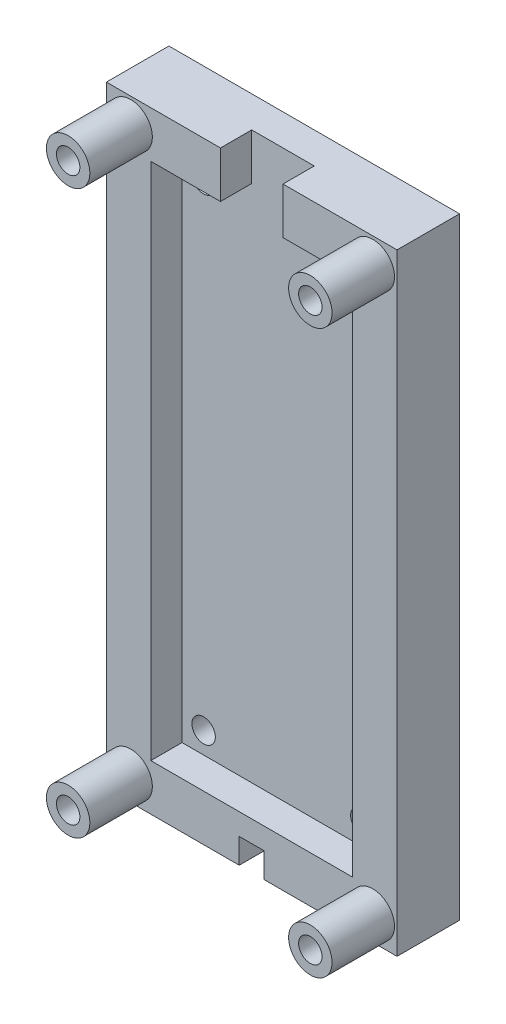
SolidWorks part; units mm, degrees
ref_plane "Front Plane" through (0, 0, 0) normal (0, 0, 1) x (1, 0, 0)
ref_plane "Top Plane" through (0, 0, 0) normal (0, 1, 0) x (1, 0, 0)
ref_plane "Right Plane" through (0, 0, 0) normal (1, 0, 0) x (0, 0, -1)
sketch "Sketch2" plane through (0, 0, 0) normal (0, 0, 1) x (1, 0, 0)
  line L0 (-7.1, -7.425) -> (-7.1, 90.475)
  line L1 (0, 0) -> (32.3, 0)
  line L2 (0, 0) -> (0, 83.05)
  line L3 (0, 83.05) -> (32.3, 83.05)
  line L4 (32.3, 0) -> (32.3, 83.05)
  line L5 (0, 0) -> (32.3, 83.05) construction
  line L6 (0, 83.05) -> (32.3, 0) construction
  line L7 (-7.1, 90.475) -> (39.4, 90.475)
  line L8 (39.4, -7.425) -> (39.4, 90.475)
  line L9 (-7.1, -7.425) -> (39.4, -7.425)
  line L10 (16.15, 3.425) -> (16.15, 79.625) construction
  line L11 (3.45, 79.625) -> (28.85, 79.625)
  line L12 (3.45, 79.625) -> (3.45, 3.425)
  line L13 (3.45, 3.425) -> (28.85, 3.425)
  line L14 (28.85, 79.625) -> (28.85, 3.425)
  line L15 (3.45, 79.625) -> (28.85, 3.425) construction
  line L16 (3.45, 3.425) -> (28.85, 79.625) construction
  line L17 (16.15, 0) -> (16.15, -7.425) construction
  line L18 (0, 41.525) -> (-7.1, 41.525) construction
  point P4 (16.15, 41.525)
  point P10 (16.15, 41.525)
  dimension "D1" = 83.05
  dimension "D2" = 32.3
  dimension "D4" = 25.4
  dimension "D5" = 76.2
  dimension "D3" = 46.5
  dimension "D6" = 97.9
extrude "Boss-Extrude1" add sketch "Sketch2" along normal mid plane 10 contours L0 L9 L8 L7 L4 L1 L2 L3 region at (-6.0162, 41.525, 0)
extrude "Boss-Extrude2" add sketch "Sketch2<4>" against normal blind 5 contours L14 L11 L12 L13 | L1 L4 L3 L2 L11 L14 L13 L12 region at (0.8911, 41.525, 0) region at (16.15, 41.525, 0)
sketch "Sketch2<4>" plane through (0, 0, 0) normal (0, 0, 1) x (1, 0, 0) same geometry as "Sketch2"
ref_axis "Axis1" through (16.15, 3.425, 0) along (0, 1, 0)
sketch "Sketch3" plane through (-7.1, 0, 0) normal (-1, 0, 0) x (0, 0, 1)
  line L0 (-5, -7.425) -> (-5, 90.475) construction
  line L1 (-5, 76.725) -> (5, 76.725)
  line L2 (-5, 76.725) -> (-5, 74.225)
  line L3 (-5, 74.225) -> (5, 74.225)
  line L4 (5, 76.725) -> (5, 74.225)
  line L5 (-5, 76.725) -> (5, 74.225) construction
  line L6 (-5, 74.225) -> (5, 76.725) construction
  line L7 (5, -7.425) -> (5, 90.475) construction
  line L8 (-5, 41.525) -> (5, 41.525) construction
  line L9 (-5, 8.825) -> (5, 8.825)
  line L10 (5, 6.325) -> (5, 8.825)
  line L11 (-5, 6.325) -> (5, 6.325)
  line L12 (-5, 6.325) -> (-5, 8.825)
  line L14 (5, 90.475) -> (-5, 90.475) construction
  point P4 (0, 75.475)
  dimension "D1" = 2.5
  dimension "D2" = 15
extrude "Boss-Extrude3" [suppressed] add sketch "Sketch3" along normal blind 2.5
ref_plane "Plane1" through (16.15, 0, 0) normal (-1, 0, 0) x (0, 0, 1)
chamfer "Chamfer1" [suppressed] distance 0.5 angle 45
mirror "Mirror2" [suppressed] about plane through (16.15, 0, 0) normal (-1, 0, 0)
sketch "Sketch4" plane through (0, 0, 0) normal (0, 0, 1) x (1, 0, 0)
  point P0 (3.45, 79.625)
  point P3 (28.85, 79.625)
  point P6 (3.45, 3.425)
  point P9 (28.85, 3.425)
hole_wizard "telemetrum-holes" positions "Sketch4" profile "Sketch5" hole size "M3x0.5" standard "ANSI Metric" end condition through all
sketch "Sketch5" plane through (3.45, 79.625, 0) normal (1, 0, 0) x (0, -1, 0)
  line L0 (0, 0) -> (0, 5)
  line L1 (0, 5) -> (1.875, 5)
  line L2 (1.875, 5) -> (1.875, 0)
  line L5 (1.875, 0) -> (0, 0)
  line L11 (0, -6.35) -> (0, 107.95) construction
  dimension "Thru Hole Dia." = 3.75
  dimension "Thru Hole Depth" = 5
sketch "Sketch7" plane through (0, 0, 0) normal (0, 0, 1) x (1, 0, 0)
  line L0 (16.15, 5.5) -> (16.15, -5.5) construction
  line L1 (-3.225, 86.525) -> (35.525, 86.525)
  line L2 (-3.225, 86.525) -> (-3.225, -3.475)
  line L3 (-3.225, -3.475) -> (35.525, -3.475)
  line L4 (35.525, 86.525) -> (35.525, -3.475)
  line L5 (16.15, -3.475) -> (16.15, 86.525) construction
  line L6 (-3.225, 41.525) -> (35.525, 41.525) construction
  line L7 (9.5243, 83.05) -> (9.5243, 86.525) construction
  line L8 (0, 83.05) -> (32.3, 83.05) construction
  line L9 (9.5243, -3.475) -> (9.5243, 0) construction
  line L10 (0, 0) -> (32.3, 0) construction
  circle A0 centre (-3.225, 86.525) radius 1.875
  circle A1 centre (35.525, 86.525) radius 1.875
  circle A2 centre (35.525, -3.475) radius 1.875
  circle A3 centre (-3.225, -3.475) radius 1.875
  circle A4 centre (-3.225, 86.525) radius 3.475
  circle A5 centre (35.525, 86.525) radius 3.475
  circle A6 centre (-3.225, -3.475) radius 3.475
  circle A7 centre (35.525, -3.475) radius 3.475
  point P480 (16.15, 41.525)
  dimension "D4" = 3.75
  dimension "D1" = 38.75
  dimension "D2" = 90
  dimension "D3" = 9.5243
  dimension "D5" = 1.6
extrude "standoffs" add sketch "Sketch7" along normal blind 15 contours L2 A6 L3 A3 | L3 A6 L2 A3 | A4 | A0 | A5 | A1 | A2 | A7 region at (-1.4713, -1.7213, 0) region at (-3.3233, -0.8, 0)
sketch "Sketch6" plane through (0, 90.475, 0) normal (0, 1, 0) x (1, 0, 0)
  line L4 (-12.2839, -5.4418) -> (-12.3348, -5.4418)
  line L5 (44.5642, -5.5441) -> (44.6151, -5.5441)
  arc A0 (44.6151, -5.5441) -> (-12.3348, -5.4418) centre (16.15, 0) cw
  arc A1 (44.5642, -5.5441) -> (-12.2839, -5.4418) centre (16.15, 0) cw
  arc A2 (44.566, -5.5346) -> (-12.2857, -5.4325) centre (16.15, 0) cw construction
  dimension "D1" = 29
  dimension "D2" = 0.05
extrude "limit-extrude" add sketch "Sketch6" against normal blind 97.55 separate body
extrude "limit-cut" cut sketch "Sketch6<2>" against normal through all both and the other way through all
sketch "Sketch6<2>" plane through (0, 90.475, 0) normal (0, 1, 0) x (1, 0, 0) same geometry as "Sketch6"
sketch "Sketch11" plane through (0, 0, 5) normal (0, 0, 1) x (1, 0, 0)
  line L0 (0, 83.05) -> (32.3, 83.05) construction
  line L1 (11.15, 75.55) -> (21.15, 75.55)
  line L2 (11.15, 75.55) -> (11.15, 90.55)
  line L3 (11.15, 90.55) -> (21.15, 90.55)
  line L4 (21.15, 75.55) -> (21.15, 90.55)
  line L5 (11.15, 75.55) -> (21.15, 90.55) construction
  line L6 (11.15, 90.55) -> (21.15, 75.55) construction
  point P0 (16.15, 83.05)
  dimension "D1" = 10
  dimension "D2" = 15
extrude "antenna-passthrough" cut sketch "Sketch11" against normal up to surface (5 mm away) and the other way through all up to face at (5.325, 79.625, 0)
sketch "Sketch12" plane through (0, 0, 5) normal (0, 0, 1) x (1, 0, 0)
  line L0 (-7.1, -7.425) -> (39.4, -7.425) construction
  line L1 (18.15, -11.425) -> (14.15, -11.425)
  line L2 (18.15, -11.425) -> (18.15, -3.425)
  line L3 (18.15, -3.425) -> (14.15, -3.425)
  line L4 (14.15, -11.425) -> (14.15, -3.425)
  line L5 (18.15, -11.425) -> (14.15, -3.425) construction
  line L6 (18.15, -3.425) -> (14.15, -11.425) construction
  point P0 (16.15, -7.425)
  dimension "D1" = 8
  dimension "D2" = 4
extrude "battery-passthrough" cut sketch "Sketch12" against normal through all
sketch "Sketch13" plane through (0, 0, 5) normal (0, 0, 1) x (1, 0, 0)
  line L0 (-3.55, 41.525) -> (35.85, 41.525)
  line L1 (16.15, 41.525) -> (16.15, 90.475) construction
  line L2 (11.15, 90.475) -> (21.15, 90.475) construction
  line L3 (16.15, 41.525) -> (16.15, -3.425) construction
  line L4 (18.15, -3.425) -> (14.15, -3.425) construction
  line L5 (-3.55, 90.475) -> (-3.55, -7.425) construction
  line L6 (-7.1, 90.475) -> (11.15, 90.475) construction
  line L7 (-7.1, -7.425) -> (14.15, -7.425) construction
  line L8 (0, 83.05) -> (-7.1, 83.05) construction
  line L9 (-7.1, -7.425) -> (-7.1, 90.475) construction
  circle A0 centre (-3.55, 41.525) radius 1.975
  circle A1 centre (35.85, 41.525) radius 1.975
  point P23 (0, 0)
  point P24 (-3.55, 83.05)
  point P25 (0, 0)
  dimension "D1" = 3.95
extrude "m4-holes" [suppressed] cut sketch "Sketch13" against normal through all both and the other way through all contours A0 | A1
